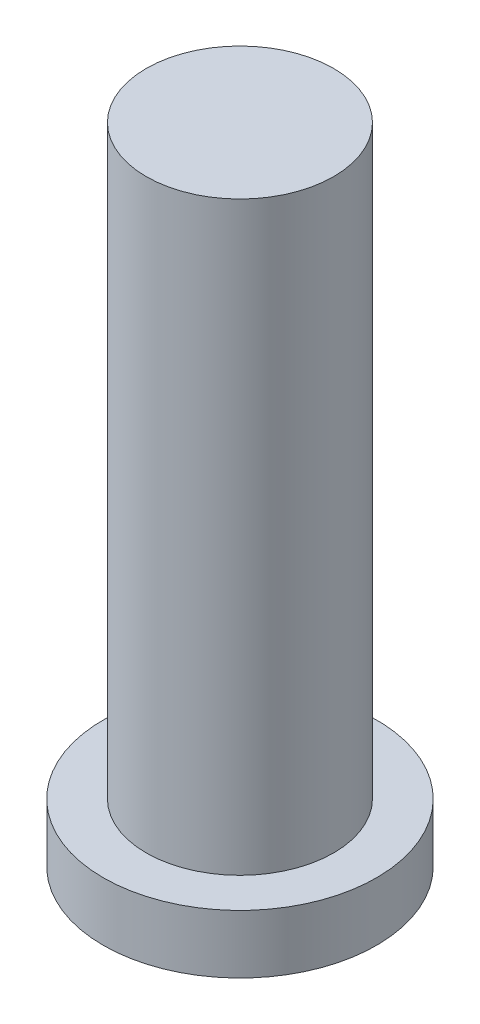
SolidWorks part; units mm, degrees
ref_plane "Front Plane" through (0, 0, 0) normal (0, 0, 1) x (1, 0, 0)
ref_plane "Top Plane" through (0, 0, 0) normal (0, 1, 0) x (1, 0, 0)
ref_plane "Right Plane" through (0, 0, 0) normal (1, 0, 0) x (0, 0, -1)
sketch "Sketch1" plane through (0, 0, 0) normal (0, 1, 0) x (1, 0, 0)
  circle A0 centre (0, 0) radius 14
  circle A1 centre (0, 0) radius 9.6
  dimension "D1" = 19.2
  dimension "D2" = 28
extrude "Boss-Extrude2" add sketch "Sketch1" along normal blind 60 contours A1
extrude "Boss-Extrude3" add sketch "Sketch1<3>" against normal blind 6 contours A0
sketch "Sketch1<3>" plane through (0, 0, 0) normal (0, 1, 0) x (1, 0, 0) same geometry as "Sketch1"
equation "\"handleTurnShaft\"= \"shaftDiam\" - \"clearance\""
equation "\"handleTurnShaftFlange\"= \"shaftDiam\" * 1.4"
equation "\"handleTurnLen\"= \"handleShaftLen\""
equation "\"handleTurnFlangeLen\"= \"handleShaftLen\" / 10"
equation "\"shaftDiam\" = 20mm"
equation "\"keyW\" = 8mm"
equation "\"keyL\" = 10mm"
equation "\"clearance\" = .8mm"
equation "\"handleShaftLen\" = 60mm"
equation "\"D2@Sketch1\"=\"handleTurnShaftFlange\""
equation "\"D1@Sketch1\"=\"handleTurnShaft\""
equation "\"D1@Boss-Extrude2\"=\"handleTurnLen\""
equation "\"D1@Boss-Extrude3\"=\"handleTurnFlangeLen\""
